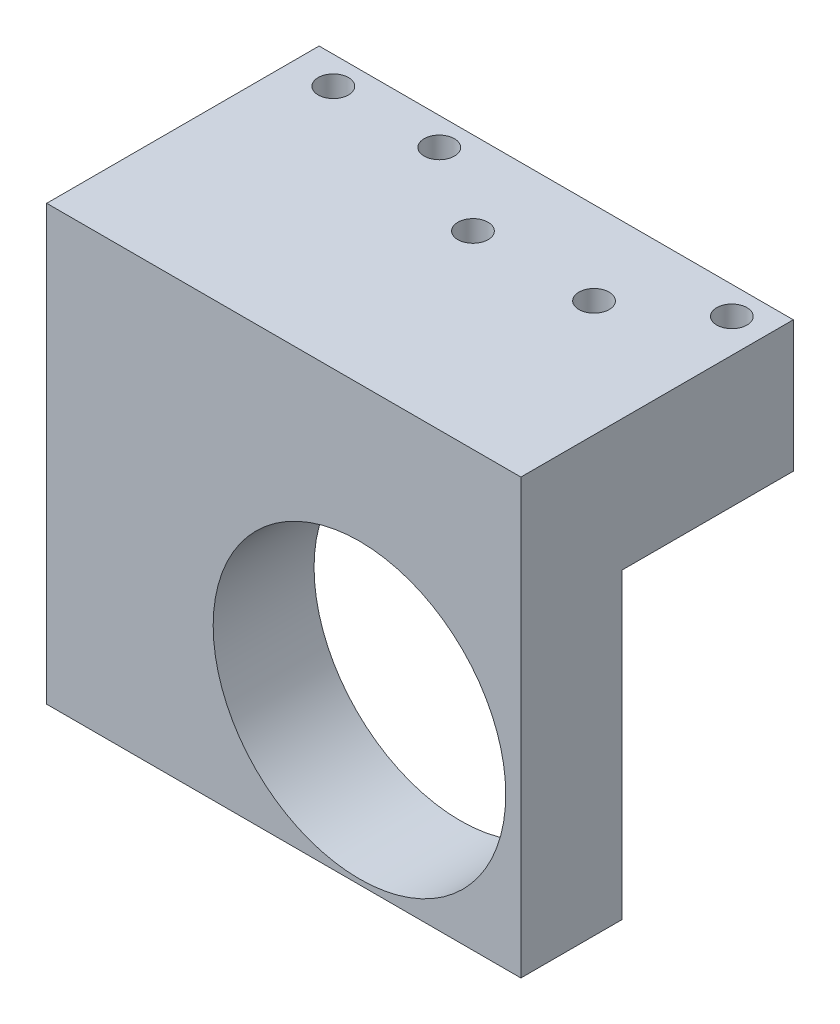
SolidWorks part; units mm, degrees
ref_plane "前视基准面" through (0, 0, 0) normal (0, 0, 1) x (1, 0, 0)
ref_plane "上视基准面" through (0, 0, 0) normal (0, 1, 0) x (1, 0, 0)
ref_plane "右视基准面" through (0, 0, 0) normal (1, 0, 0) x (0, 0, -1)
other "Configuration Table"
sketch "草图1" plane through (0, 0, 0) normal (0, 1, 0) x (1, 0, 0)
  line L0 (-23.5, -5.5) -> (-23.5, -21.5)
  line L1 (-23.5, 5.5) -> (23.5, 5.5)
  line L2 (-23.5, 5.5) -> (-23.5, -5.5)
  line L4 (23.5, 5.5) -> (23.5, -5.5)
  line L5 (-23.5, 5.5) -> (23.5, -5.5) construction
  line L6 (-23.5, -5.5) -> (23.5, 5.5) construction
  line L7 (-23.5, -21.5) -> (23.5, -21.5)
  line L8 (23.5, -21.5) -> (23.5, -5.5)
  circle A6 centre (20.1592, 2.75) radius 1.5
  circle A7 centre (-8.8408, 2.75) radius 1.5
  circle A8 centre (-19.3408, 2.75) radius 1.5
  circle A9 centre (0, -2.75) radius 1.5
  circle A10 centre (12, -2.75) radius 1.5
  point P0 (0, 0)
  dimension "D3" = 3
  dimension "D4" = 2.75
  dimension "D6" = 3
  dimension "D1" = 11
  dimension "D2" = 47
  dimension "D7" = 12
  dimension "D8" = 16
extrude "凸台-拉伸1" add sketch "草图1" along normal blind 13
sketch "草图2" plane through (0, 0, 21.5) normal (0, 0, 1) x (1, 0, 0)
  line L1 (-23.5, 0) -> (23.5, 0)
  line L2 (-23.5, 0) -> (-23.5, -30)
  line L3 (-23.5, -30) -> (23.5, -30)
  line L4 (23.5, 0) -> (23.5, -30)
  circle A0 centre (7.5, -15) radius 14.5
extrude "凸台-拉伸2" add sketch "草图2" against normal blind 10
